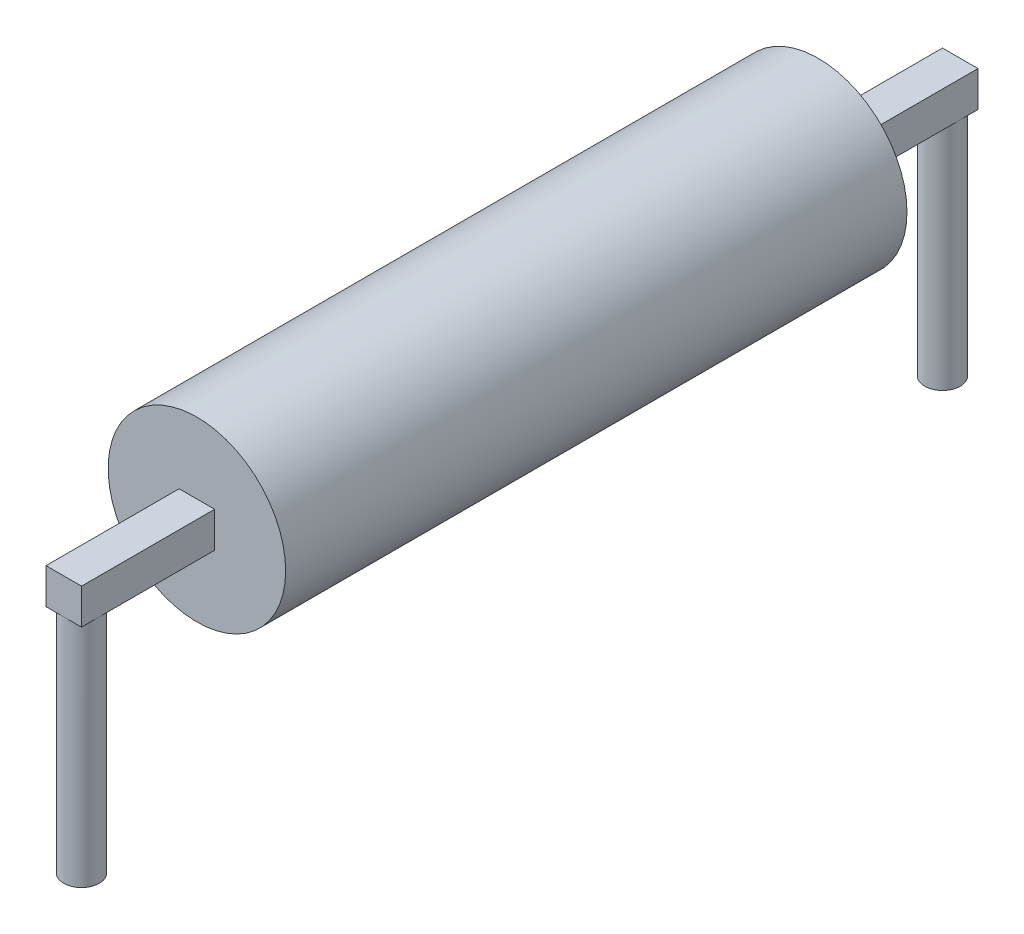
SolidWorks part; units mm, degrees
ref_plane "Спереди" through (0, 0, 0) normal (0, 0, 1) x (1, 0, 0)
ref_plane "Сверху" through (0, 0, 0) normal (0, 1, 0) x (1, 0, 0)
ref_plane "Справа" through (0, 0, 0) normal (1, 0, 0) x (0, 0, -1)
sketch "Эскиз1" plane through (0, 0, 0) normal (0, 0, 1) x (1, 0, 0)
  circle A0 centre (0, 0) radius 2.5
  dimension "D1" = 5
extrude "Вытянуть1" add sketch "Эскиз1" along normal blind 17.5
sketch "Эскиз2" plane through (0, 0, 17.5) normal (0, 0, 1) x (1, 0, 0)
  line L0 (0, 0.6747) -> (0, -0.3959) construction
  line L1 (-0.5, -0.5) -> (0.5, -0.5)
  line L2 (-0.5, -0.5) -> (-0.5, 0.5)
  line L3 (-0.5, 0.5) -> (0.5, 0.5)
  line L4 (0.5, -0.5) -> (0.5, 0.5)
  line L5 (-0.474, 0) -> (0.6636, 0) construction
  dimension "D2" = 1
extrude "Вытянуть2" add sketch "Эскиз2" along normal blind 3.75 and the other way blind 21.5
sketch "Эскиз3" plane through (0, -0.5, 0) normal (0, -1, 0) x (1, 0, 0)
  line L0 (0, 17.5) -> (0, 0) construction
  line L1 (-0.5, 21.25) -> (0.5, 21.25) construction
  line L2 (-0.5, -4) -> (0.5, -4) construction
  circle A0 centre (0, 20.75) radius 0.5
  circle A1 centre (0, -3.5) radius 0.5
  dimension "D1" = 1
extrude "Вытянуть3" add sketch "Эскиз3" along normal blind 6.5
